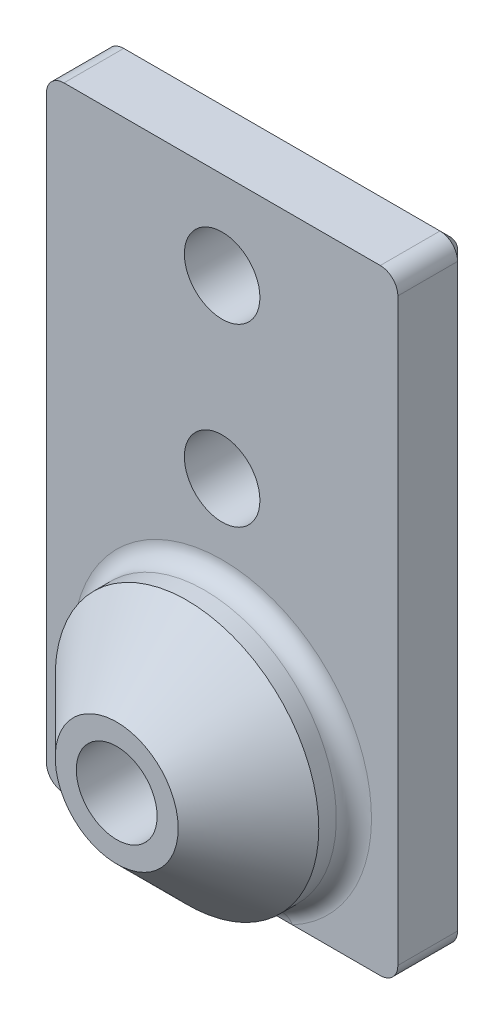
SolidWorks part; units mm, degrees
ref_plane "Front Plane" through (0, 0, 0) normal (0, 0, 1) x (1, 0, 0)
ref_plane "Top Plane" through (0, 0, 0) normal (0, 1, 0) x (1, 0, 0)
ref_plane "Right Plane" through (0, 0, 0) normal (1, 0, 0) x (0, 0, -1)
sketch "Sketch1" plane through (0, 0, 0) normal (0, 0, 1) x (1, 0, 0)
  line L0 (-10, 35) -> (-10, 0) construction
  line L1 (0, 0) -> (-20, 0)
  line L2 (0, 0) -> (0, 35)
  line L3 (0, 35) -> (-20, 35)
  line L4 (-20, 0) -> (-20, 35)
  circle A0 centre (-10, 30) radius 2.15
  circle A1 centre (-10, 20) radius 2.15
  point P11 (-10, 13.7116)
  point P12 (-10, 30.0066)
  point P13 (-10, 34.668)
  point P14 (-10, 23.674)
  point P15 (-10, 22.0503)
  dimension "D3" = 4.3
  dimension "D1" = 20
  dimension "D2" = 35
  dimension "D4" = 10
  dimension "D5" = 5
extrude "Boss-Extrude1" add sketch "Sketch1" along normal blind 4
sketch "Sketch2" plane through (0, 0, 4) normal (0, 0, 1) x (1, 0, 0)
  line L5 (-20, 0) -> (0, 0) construction
  line L6 (0, 0) -> (0, 15) construction
  line L7 (0, 0) -> (0, 35) construction
  line L8 (0, 15) -> (-20, 15) construction
  line L9 (-20, 35) -> (-20, 0) construction
  line L10 (-20, 15) -> (-20, 0) construction
  line L11 (-20, 0) -> (0, 15) construction
  circle A0 centre (-10, 7.5) radius 7.5
  dimension "D1" = 15
extrude "Boss-Extrude2" add sketch "Sketch2" along normal blind 6
sketch "Sketch3" plane through (0, 0, 10) normal (0, 0, 1) x (1, 0, 0)
  circle A1 centre (-10, 7.5) radius 2.3
  dimension "D1" = 4.6
extrude "Cut-Extrude1" cut sketch "Sketch3" against normal blind 7
chamfer "Chamfer1" distance 4 angle 45 1 edges at (-2.5, 7.5, 10)
fillet "Fillet1" radius 1 5 edges at (-2.5, 7.5, 4) (0, 35, 2) (-20, 35, 2) (-20, 0, 2) (0, 0, 2)
chamfer "Chamfer2" distance 0.6 angle 45 10 edges at (-7.85, 20, 0) (-7.85, 30, 0) (-19.7071, 34.7071, 0) (-20, 17.5, 0) (-19.7071, 0.2929, 0) (-10, 0, 0) (-0.2929, 0.2929, 0) (0, 17.5, 0) (-0.2929, 34.7071, 0) (-10, 35, 0)
